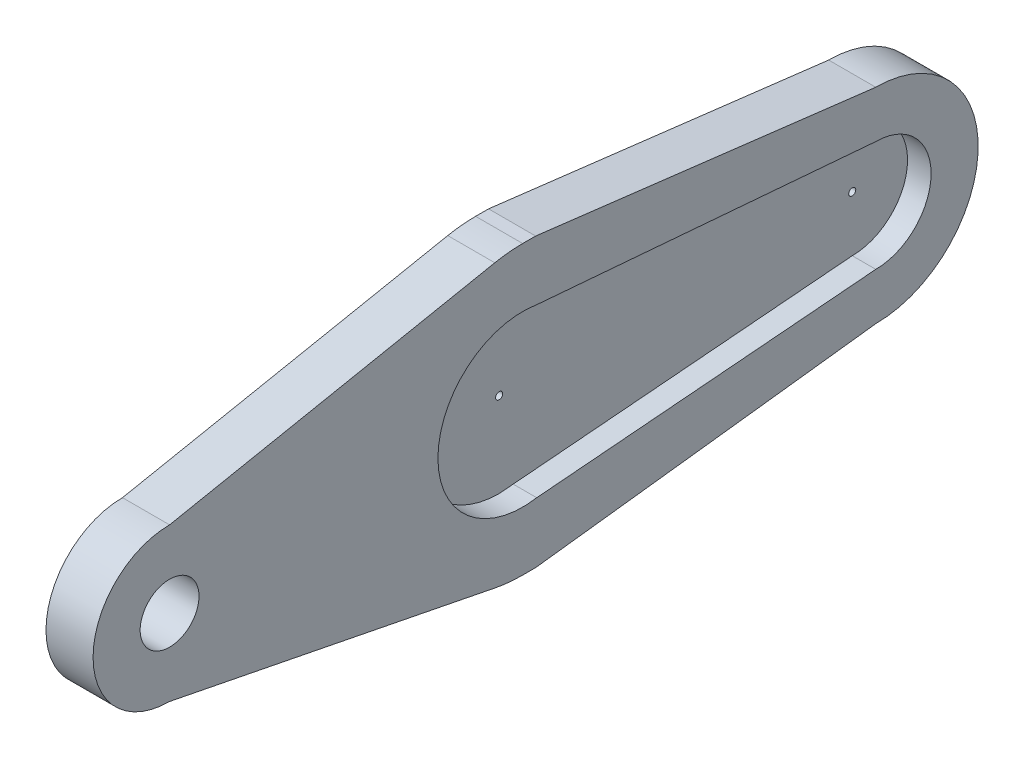
SolidWorks part; units mm, degrees
ref_plane "Front Plane" through (0, 0, 0) normal (1, 0, 0) x (0, 1, 0)
ref_plane "Top Plane" through (0, 0, 0) normal (0, 0, 1) x (0, 1, 0)
ref_plane "Right Plane" through (0, 0, 0) normal (0, 1, 0) x (-1, 0, 0)
sketch "Sketch2" plane through (0, 0, 0) normal (1, 0, 0) x (0, 1, 0)
  line L0 (0, -13.9832) -> (0, -33.5576) construction
  line L1 (-6.1, -18.8) -> (6.1, -18.8)
  line L2 (-6.1, -18.8) -> (-6.1, 18.8)
  line L3 (-6.1, 18.8) -> (6.1, 18.8)
  line L4 (6.1, -18.8) -> (6.1, 18.8)
  line L5 (-6.1, -18.8) -> (6.1, 18.8) construction
  line L6 (-6.1, 18.8) -> (6.1, -18.8) construction
  line L7 (2.35, -14.45) -> (3.6, 0.55)
  line L8 (-3.6, 0.55) -> (-2.35, -14.45)
  line L9 (-6.1, 0) -> (-4.35, -14.45)
  line L10 (4.35, -14.45) -> (6.1, 0)
  line L11 (-3.25, 15.55) -> (-5.984, 1.7341)
  line L12 (5.984, 1.7341) -> (3.25, 15.55)
  arc A1 (3.5503, -0.0459) -> (-3.5503, -0.0459) centre (0, 0.55) ccw
  arc A2 (-2.35, -14.45) -> (2.35, -14.45) centre (0, -14.45) ccw
  circle A3 centre (0, 15.55) radius 1.25
  arc A4 (3.25, 15.55) -> (-3.25, 15.55) centre (0, 15.55) ccw
  arc A5 (-4.35, -14.45) -> (4.35, -14.45) centre (0, -14.45) ccw
  arc A6 (-5.984, 1.7341) -> (-6.1, 0.55) centre (0, 0.55) ccw
  arc A7 (6.1, 0.55) -> (5.984, 1.7341) centre (0, 0.55) ccw
  point P0 (0, 0)
  point P13 (0, 0)
  dimension "D1" = 7.2
  dimension "D2" = 4.7
  dimension "D4" = 2.5
  dimension "D5" = 2
  dimension "D8" = 2
  dimension "D3" = 15
  dimension "D6" = 15
  dimension "D7" = 2.5
extrude "Boss-Extrude1" add sketch "Sketch2" along normal blind 2 contours L4 A7 L12 A4 L11 A6 L2 L9 A5 L10 A3 A2 L8 A1 L7 region at (0, -2.7964, -17.2464)
extrude "Boss-Extrude2" add sketch "Sketch2<3>" along normal blind 1 contours L8 A2 L7 A1 region at (0, 0, -5.6231)
sketch "Sketch2<3>" plane through (0, 0, 0) normal (1, 0, 0) x (0, 1, 0) same geometry as "Sketch2"
sketch "Sketch3" plane through (1, 0, 0) normal (1, 0, 0) x (0, 1, 0)
  circle A0 centre (0, 0.55) radius 0.15
  arc A1 (3.6, 0.55) -> (-3.6, 0.55) centre (0, 0.55) ccw construction
  circle A2 centre (0, -14.45) radius 0.15
  arc A3 (-2.35, -14.45) -> (2.35, -14.45) centre (0, -14.45) ccw construction
  dimension "D1" = 0.3
extrude "Cut-Extrude1" cut sketch "Sketch3" against normal blind 0.5
